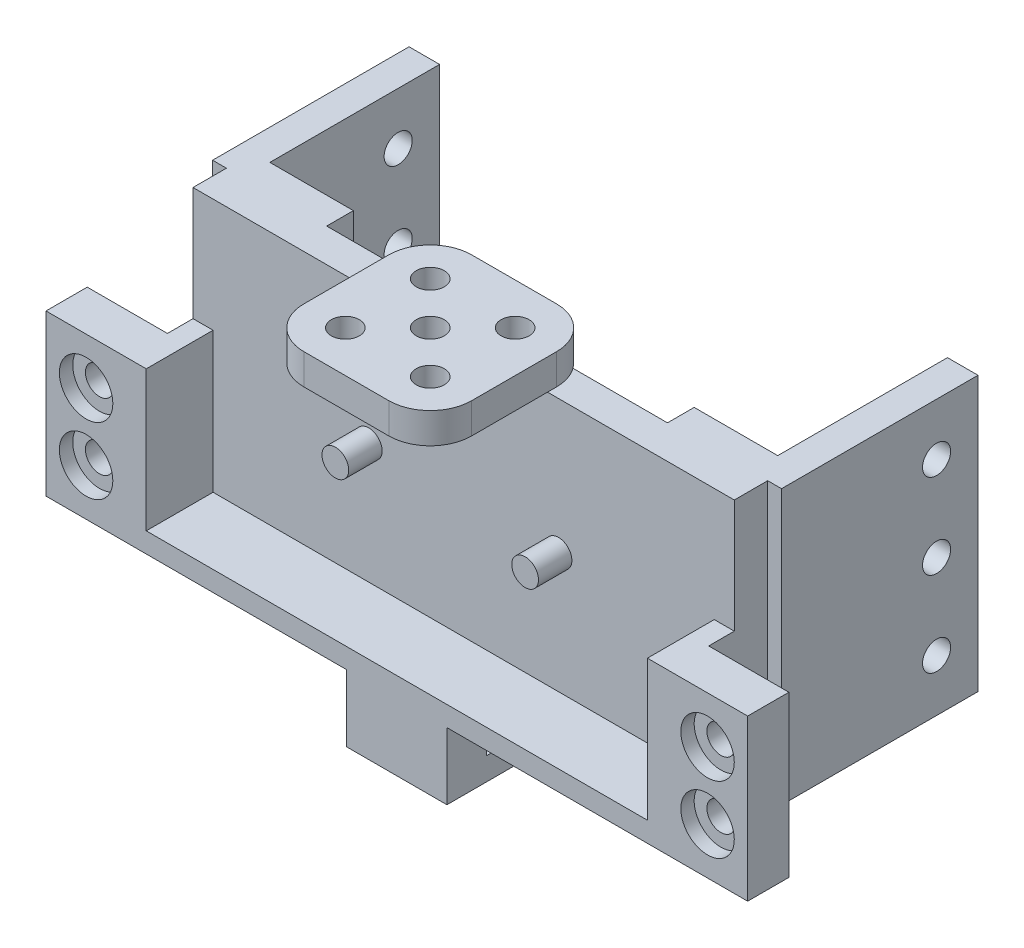
SolidWorks part; units mm, degrees
ref_plane "Front Plane" through (0, 0, 0) normal (0, 0, 1) x (1, 0, 0)
ref_plane "Top Plane" through (0, 0, 0) normal (0, 1, 0) x (1, 0, 0)
ref_plane "Right Plane" through (0, 0, 0) normal (1, 0, 0) x (0, 0, -1)
sketch "Sketch1" plane through (0, 0, 0) normal (0, 0, 1) x (1, 0, 0)
  line L1 (-37.5, -17.5) -> (37.5, -17.5)
  line L2 (-37.5, -17.5) -> (-37.5, 17.5)
  line L3 (-37.5, 17.5) -> (37.5, 17.5)
  line L4 (37.5, -17.5) -> (37.5, 17.5)
  line L5 (-37.5, -17.5) -> (37.5, 17.5) construction
  line L6 (-37.5, 17.5) -> (37.5, -17.5) construction
  point P0 (0, 0)
  dimension "D1" = 75
  dimension "D2" = 35
extrude "Boss-Extrude1" add sketch "Sketch1" along normal blind 5
sketch "Sketch2" plane through (0, 0, 5) normal (0, 0, 1) x (1, 0, 0)
  circle A0 centre (-14.2, 0.5) radius 2
  circle A1 centre (14.2, 0.5) radius 2
  dimension "D4" = 4
  dimension "D5" = 4
extrude "Boss-Extrude2" add sketch "Sketch2" along normal blind 10
sketch "Sketch3" plane through (0, 0, 0) normal (0, 0, -1) x (-1, 0, 0)
  line L1 (-37.5, 17.5) -> (37.5, 17.5)
  line L2 (-37.5, 17.5) -> (-37.5, -17.5)
  line L3 (-37.5, -17.5) -> (37.5, -17.5)
  line L4 (37.5, 17.5) -> (37.5, -17.5)
  line L5 (-37.5, 20.5) -> (-40.5, 20.5)
  line L6 (40.5, -17.5) -> (40.5, -20.5)
  line L8 (-40.5, 20.5) -> (40.5, 20.5)
  line L9 (-40.5, 20.5) -> (-40.5, -20.5)
  line L10 (-40.5, -20.5) -> (40.5, -20.5)
  line L11 (40.5, 20.5) -> (40.5, -20.5)
  line M1 (-37.5, 17.5) -> (-37.5, -17.5)
  line M2 (-37.5, -17.5) -> (37.5, -17.5)
  line M3 (37.5, -17.5) -> (37.5, 17.5)
  line M4 (37.5, 17.5) -> (-37.5, 17.5)
extrude "Boss-Extrude3" add sketch "Sketch3" against normal blind 15 contours L11 L8 L5 L9 L10 L6 M1 M4 M3 M2 region at (-1.5, 19.5921, 0)
sketch "Sketch4" plane through (0, 20.5, 0) normal (0, 1, 0) x (1, 0, 0)
  line L0 (-37.5, -5) -> (-37.5, -12.5)
  line L2 (-37.5, -15) -> (37.5, -15)
  line L4 (37.5, -5) -> (37.5, -12.5)
  line L5 (-37.5, -14) -> (-37.5, -15)
  line L12 (-37.5, -12.5) -> (-37.5, -14)
  line L14 (37.5, -14) -> (37.5, -12.5)
  line L16 (37.5, -15) -> (37.5, -14)
  line L17 (-37.5, -5) -> (37.5, -5)
  dimension "D2" = 1
  dimension "D3" = 1.5
extrude "Cut-Extrude2" cut sketch "Sketch4" against normal blind 10
sketch "Sketch8" plane through (0, 20.5, 0) normal (0, 1, 0) x (1, 0, 0)
  line L0 (0, -5) -> (0, 2.55)
  line L1 (37.5, -5) -> (-37.5, -5) construction
  line L3 (0, -5) -> (0, -15)
  line L4 (0, -15) -> (0, -22.55)
  line L16 (0, 2.55) -> (-12.55, 2.55)
  line L17 (0, 2.55) -> (12.55, 2.55)
  line L18 (0, -22.55) -> (-12.55, -22.55)
  line L19 (0, -22.55) -> (12.55, -22.55)
  line L21 (-12.55, 2.55) -> (12.55, 2.55)
  line L22 (-12.55, 2.55) -> (-12.55, -22.55)
  line L23 (-12.55, -22.55) -> (12.55, -22.55)
  line L24 (12.55, 2.55) -> (12.55, -22.55)
  line M6 (-37.5, -5) -> (37.5, -5)
  line M10 (40.5, 0) -> (-40.5, 0)
  dimension "D1" = 7.55
  dimension "D2" = 10
  dimension "D3" = 7.55
  dimension "D5" = 12.55
extrude "Boss-Extrude6" add sketch "Sketch8" along normal blind 4.57 contours L22 L18 L4 L3 M6 | L24 L3 L4 L19 M6 | L22 L0 M10 M6 | L16 L22 L0 M10 | L24 L17 L0 M10 | L24 L0 M10 M6 region at (-6.275, 20.5, 2.5) region at (6.275, 20.5, 13.775) region at (-6.275, 20.5, 13.775) region at (6.275, 20.5, 2.5) region at (-6.275, 20.5, -1.275) region at (6.275, 20.5, -1.275)
sketch "Sketch9" plane through (0, 25.07, 0) normal (0, 1, 0) x (1, 0, 0)
  circle A0 centre (0, -10) radius 2.1
  circle A1 centre (-6.3498, -3.6502) radius 2.1
  circle A2 centre (6.3498, -3.6502) radius 2.1
  circle A3 centre (6.3498, -16.3498) radius 2.1
  circle A4 centre (-6.3498, -16.3498) radius 2.1
  dimension "D1" = 4.2
  dimension "D2" = 4.2
  dimension "D3" = 4.2
  dimension "D4" = 4.2
  dimension "D5" = 4.2
  dimension "D6" = 8.98
  dimension "D7" = 8.98
  dimension "D8" = 8.98
  dimension "D9" = 8.98
extrude "Cut-Extrude3" cut sketch "Sketch9" against normal blind 4.57
sketch "Sketch14" plane through (0, 20.5, 0) normal (0, 1, 0) x (1, 0, 0)
  line L1 (-37.5, -5) -> (-40.5, -5)
  line L2 (-37.5, -5) -> (-37.5, -15)
  line L3 (-37.5, -15) -> (-40.5, -15)
  line L4 (-40.5, -5) -> (-40.5, -15)
  line L5 (37.5, -5) -> (40.5, -5)
  line L6 (37.5, -5) -> (37.5, -15)
  line L7 (37.5, -15) -> (40.5, -15)
  line L8 (40.5, -5) -> (40.5, -15)
extrude "Cut-Extrude5" cut sketch "Sketch14" against normal blind 17
sketch "Sketch15" plane through (0, 20.5, 0) normal (0, 1, 0) x (1, 0, 0)
  circle A0 centre (-6.3498, -3.6502) radius 2.75
  circle A1 centre (6.3498, -3.6502) radius 2.75
  dimension "D1" = 5.5
  dimension "D2" = 5.5
extrude "Cut-Extrude6" cut sketch "Sketch15" against normal blind 1.5
fillet "Fillet1" radius 1 4 edges at (-8.7458, 19.75, 5) (3.9539, 19.75, 5) (8.7458, 19.75, 5) (-3.9539, 19.75, 5)
sketch "Sketch19" plane through (0, 0, 15) normal (0, 0, 1) x (1, 0, 0)
  circle A0 centre (-14.2, 0.5) radius 2
extrude "Cut-Extrude7" cut sketch "Sketch19" against normal blind 5
sketch "Sketch20" plane through (40.5, 0, 0) normal (1, 0, 0) x (0, 0, -1)
  line L0 (-15, 3.5) -> (-5, 3.5) construction
  line L1 (-15, -20.5) -> (-8.83, -20.5)
  line L2 (-15, -20.5) -> (-15, 3.5)
  line L3 (-15, 3.5) -> (-8.83, 3.5)
  line L4 (-8.83, -20.5) -> (-8.83, 3.5)
  dimension "D1" = 6.17
extrude "Boss-Extrude7" add sketch "Sketch20" along normal blind 12
sketch "Sketch21" plane through (-40.5, 0, 0) normal (-1, 0, 0) x (0, 0, 1)
  line L0 (15, -20.5) -> (0, -20.5) construction
  line L1 (15, 3.5) -> (8.83, 3.5)
  line L2 (15, 3.5) -> (15, -20.5)
  line L3 (15, -20.5) -> (8.83, -20.5)
  line L4 (8.83, 3.5) -> (8.83, -20.5)
  dimension "D1" = 6.17
extrude "Boss-Extrude8" add sketch "Sketch21" along normal blind 12
sketch "Sketch24" plane through (0, 0, 8.83) normal (0, 0, -1) x (-1, 0, 0)
  line L0 (-46.5, 3.5) -> (-46.5, -5.6) construction
  line L1 (-46.5, -5.6) -> (-46.5, 3.5) construction
  line L2 (-46.5, -10.6) -> (-46.5, -20.5) construction
  line L3 (-52.5, 3.5) -> (-40.5, 3.5) construction
  line L4 (-46.5, -10.6) -> (-46.5, -20.5) construction
  line L5 (46.5, -10.6) -> (46.5, -20.5) construction
  line L6 (-52.5, -20.5) -> (-40.5, -20.5) construction
  line L7 (46.5, 3.5) -> (46.5, -6.4) construction
  line L8 (52.5, 3.5) -> (40.5, 3.5) construction
  line L9 (52.5, -20.5) -> (40.5, -20.5) construction
  circle A1 centre (-46.5, -3.5) radius 2.1
  circle A2 centre (-46.5, -13.5) radius 2.1
  circle A4 centre (46.5, -3.5) radius 2.1
  circle A5 centre (46.5, -13.5) radius 2.1
  dimension "D1" = 4.2
  dimension "D2" = 7
  dimension "D3" = 4.2
  dimension "D4" = 4.2
  dimension "D5" = 9.9
  dimension "D6" = 4.2
  dimension "D7" = 7
  dimension "D8" = 7
  dimension "D9" = 7
extrude "Cut-Extrude8" cut sketch "Sketch24" against normal through all
sketch "Sketch25" plane through (0, 0, 15) normal (0, 0, 1) x (1, 0, 0)
  circle A6 centre (-46.5, -3.5) radius 4
  circle A7 centre (-46.5, -13.5) radius 4
  circle A8 centre (46.5, -13.5) radius 4
  circle A9 centre (46.5, -3.5) radius 4
  dimension "D1" = 8
  dimension "D2" = 8
  dimension "D3" = 8
  dimension "D4" = 8
extrude "Cut-Extrude9" cut sketch "Sketch25" against normal blind 2
sketch "Sketch28" plane through (0, -20.5, 0) normal (0, -1, 0) x (1, 0, 0)
  line L0 (-25.5, 0) -> (-42.57, 0)
  line L1 (40.5, 0) -> (-40.5, 0) construction
  line L2 (-42.57, 0) -> (-42.57, -29.4)
  line L3 (25.5, 0) -> (42.57, 0)
  line L4 (40.5, 0) -> (-40.5, 0) construction
  line L5 (42.57, 0) -> (42.57, -29.4)
  line L6 (-42.57, -29.4) -> (-38, -29.4)
  line L7 (-38, -29.4) -> (-38, -4)
  line L8 (-38, -4) -> (-25.5, -4)
  line L9 (-25.5, -4) -> (-25.5, 0)
  line L10 (42.57, -29.4) -> (38, -29.4)
  line L11 (38, -29.4) -> (38, -4)
  line L12 (38, -4) -> (25.5, -4)
  line L13 (25.5, -4) -> (25.5, 0)
  line L14 (40.5, 8.83) -> (40.5, 0) construction
  line L15 (-40.5, 8.83) -> (-40.5, 0) construction
  dimension "D1" = 29.4
  dimension "D2" = 29.4
  dimension "D3" = 81
  dimension "D4" = 4
  dimension "D5" = 4
  dimension "D6" = 4.57
  dimension "D7" = 4.57
  dimension "D8" = 15
  dimension "D9" = 15
  dimension "D10" = 38
  dimension "D11" = 38
extrude "Boss-Extrude10" add sketch "Sketch28" against normal blind 41
sketch "Sketch30" plane through (-38, 0, 0) normal (1, 0, 0) x (0, 0, -1)
  line L1 (29.4, 0) -> (23.2, 0)
  line L2 (29.4, 20.5) -> (29.4, -20.5) construction
  circle A0 centre (23.2, 0) radius 2.1
  circle A1 centre (23.2, 12.7) radius 2.1
  circle A2 centre (23.2, -12.7) radius 2.1
  dimension "D2" = 4.2
  dimension "D3" = 4.2
  dimension "D4" = 4.2
  dimension "D1" = 6.2
  dimension "D5" = 12.7
  dimension "D6" = 12.7
extrude "Cut-Extrude11" cut sketch "Sketch30" along normal through all and the other way through all contours A2 | A0 | A1 region at (-38, 0, -21.1594) region at (-38, 12.7, -23.2) region at (-38, -12.7, -23.2)
fillet "Fillet2" radius 6.2 4 edges at (-12.55, 22.785, -2.55) (12.55, 22.785, -2.55) (12.55, 22.785, 22.55) (-12.55, 22.785, 22.55)
sketch "Sketch31" plane through (0, -20.5, 0) normal (0, -1, 0) x (1, 0, 0)
  line L0 (52.5, 15) -> (-52.5, 15) construction
  line L1 (-7.5, 15) -> (7.5, 15)
  line L2 (-7.5, 15) -> (-7.5, 0)
  line L3 (-7.5, 0) -> (7.5, 0)
  line L4 (7.5, 15) -> (7.5, 0)
  line L5 (11.3617, 0) -> (-11.3617, 0) construction
  point P8 (0, 15)
extrude "Boss-Extrude11" add sketch "Sketch31" along normal blind 10 contours L4 L3 L2 L1
sketch "Sketch32" plane through (0, -30.5, 0) normal (0, -1, 0) x (1, 0, 0)
  line L1 (-2.5, 13.5) -> (2.5, 13.5)
  line L2 (-2.5, 13.5) -> (-2.5, 1.5)
  line L3 (-2.5, 1.5) -> (2.5, 1.5)
  line L4 (2.5, 13.5) -> (2.5, 1.5)
  point P4 (0, 0)
  dimension "D1" = 5
  dimension "D2" = 12
  dimension "D3" = 1.5
  dimension "D4" = 5
extrude "Cut-Extrude12" cut sketch "Sketch32" against normal blind 10 contours L2 L3 L4 L1
sketch "Sketch34" plane through (-7.5, 0, 0) normal (-1, 0, 0) x (0, 0, 1)
  line L0 (5.9, -23.9) -> (9.1, -27.1) construction
  line L1 (5.9, -23.9) -> (9.1, -23.9)
  line L2 (5.9, -23.9) -> (5.9, -27.1)
  line L3 (5.9, -27.1) -> (9.1, -27.1)
  line L4 (9.1, -23.9) -> (9.1, -27.1)
  line L5 (9.1, -23.9) -> (5.9, -27.1) construction
  line L6 (0, -20.5) -> (15, -30.5) construction
  line L7 (0, -30.5) -> (15, -20.5) construction
  point P10 (7.5, -25.5)
  point P13 (7.5, -25.5)
  dimension "D1" = 3.2
  dimension "D2" = 3.2
extrude "Cut-Extrude13" cut sketch "Sketch34" against normal blind 28
sketch "Sketch35" plane through (0, 0, 15) normal (0, 0, 1) x (1, 0, 0)
  circle A0 centre (14.2, 0.5) radius 2
extrude "Cut-Extrude14" cut sketch "Sketch35" against normal blind 5
